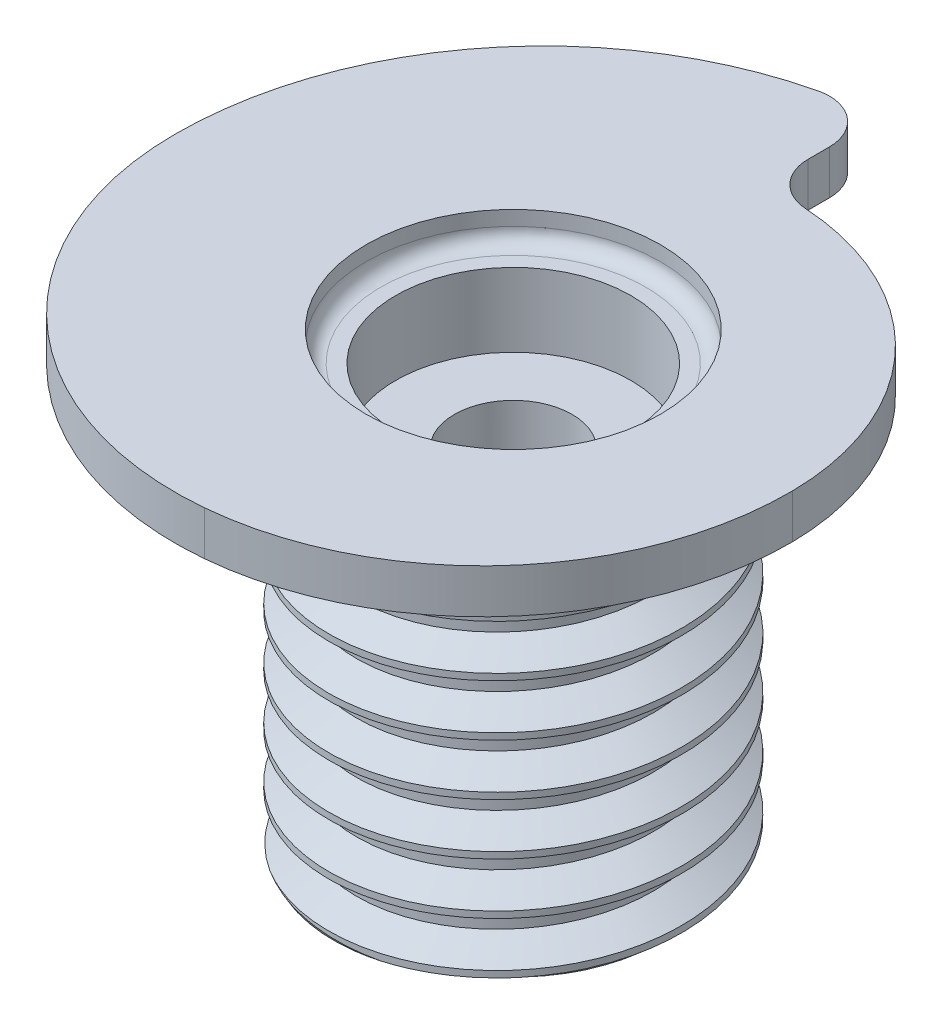
SolidWorks part; units mm, degrees
ref_plane "Front Plane" through (0, 0, 0) normal (0, 0, 1) x (1, 0, 0)
ref_plane "Top Plane" through (0, 0, 0) normal (0, 1, 0) x (1, 0, 0)
ref_plane "Right Plane" through (0, 0, 0) normal (1, 0, 0) x (0, 0, -1)
sketch "Sketch1" plane through (0, 0, 0) normal (1, 0, 0) x (0, 0, -1)
  line L4 (12, 28) -> (12, 0)
  line L6 (0, 0) -> (0, 28) construction
  line L7 (12, 28) -> (4, 28)
  line L10 (4, 28) -> (4, 5)
  line L11 (4, 5) -> (8, 5)
  line L12 (8, 5) -> (8, 0)
  line L13 (8, 0) -> (12, 0)
  dimension "D1" = 8
  dimension "D2" = 8
  dimension "D3" = 5
  dimension "D6" = 28
  dimension "D7" = 12
revolve "Revolve1" add sketch "Sketch1" angle 360 about L6
chamfer "Chamfer1" distance 1 angle 30 1 edges at (0, 0, -12) first distance on face at (0, 28, -12)
thread "Thread1" pitch 3.5 method cut profile "Thread Profile1" start angle 0, offset 0, length 48, pitch 3.5, diameter 24
ref_plane "Plane1" through (-12, 28, 0) normal (0, 0, 1) x (-1, 0, 0)
sketch "Thread Profile1" plane through (-12, 28, 0) normal (0, 0, 1) x (-1, 0, 0)
  line L0 (0, 0) -> (0, 3.5) construction
  line L11 (0, 0) -> (0, 3.0625)
  line L12 (0, 3.0625) -> (-1.8944, 1.9687)
  line L13 (-1.8944, 1.9687) -> (-1.8944, 1.0937)
  line L15 (-1.8944, 1.0937) -> (0, 0)
  line L17 (-1.8944, 1.5312) -> (0, 1.5312) construction
  point P2 (0, 0)
  dimension "Pitch" = 3.5
  dimension "Profile_Angle" = 60
  dimension "Profile_Land" = 0.875
  dimension "Profile_Height" = 1.8944
sketch "Sketch2" plane through (0, 28, 0) normal (0, 1, 0) x (1, 0, 0)
  line L1 (0, 11.547) -> (-10, -5.7735) construction
  line L2 (-10, -5.7735) -> (10, -5.7735) construction
  line L3 (10, -5.7735) -> (0, 11.547) construction
  circle A0 centre (0, 0) radius 5.7735 construction
  circle A1 centre (0, 11.547) radius 1.5
  circle A2 centre (10, -5.7735) radius 1.5
  circle A3 centre (-10, -5.7735) radius 1.5
  dimension "D2" = 3
  dimension "D1" = 20
extrude "Cut-Extrude1" [suppressed] cut sketch "Sketch2" against normal blind 4
sketch "Sketch3" plane through (0, 28, 0) normal (0, 1, 0) x (1, 0, 0)
  line L0 (0, 25) -> (0, -25) construction
  line L1 (-25, 0) -> (25, 0) construction
  line L2 (0, 25) -> (0, 17)
  circle A1 centre (0, 0) radius 17 construction
  circle A2 centre (0, 0) radius 19 construction
  circle A3 centre (0, 0) radius 21 construction
  circle A4 centre (0, 0) radius 23 construction
  circle A5 centre (0, 0) radius 25 construction
  arc A6 (0, 25) -> (-23, 0) centre (2.087, 0) ccw
  arc A7 (-23, 0) -> (0, -21) centre (-1.913, 0) ccw
  arc A8 (0, -21) -> (19, 0) centre (-1.8958, -0.1895) ccw
  arc A9 (19, 0) -> (0, 17) centre (1.7548, -0.1564) ccw
  dimension "D1" = 34
  dimension "D2" = 2
  dimension "D3" = 2
  dimension "D4" = 2
  dimension "D5" = 2
extrude "Boss-Extrude1" add sketch "Sketch3" along normal blind 3
sketch "Sketch6" plane through (0, 31, 0) normal (0, 1, 0) x (1, 0, 0)
  circle A0 centre (0, 0) radius 10
  dimension "D1" = 20
extrude "Cut-Extrude3" cut sketch "Sketch6" against normal blind 2
sketch "Sketch4" plane through (0, 29, 0) normal (0, 1, 0) x (1, 0, 0)
  circle A2 centre (0, 0) radius 8
  dimension "D1" = 16
extrude "Cut-Extrude2" cut sketch "Sketch4" against normal blind 5
fillet "Fillet1" radius 3 2 edges at (0, 29.5, -17) (0, 29.5, -25)
sketch "Sketch5" plane through (0, 31, 0) normal (0, 1, 0) x (1, 0, 0)
  arc A0 (-6.606, 16.744) -> (-18, 0) centre (0, 0) ccw construction
  arc A1 (-7.5235, 19.0695) -> (-20.5, 0) centre (0, 0) ccw
  arc A2 (-5.6885, 14.4184) -> (-15.5, 0) centre (0, 0) ccw
  arc A3 (-5.6885, 14.4184) -> (-7.5235, 19.0695) centre (-6.606, 16.744) ccw
  arc A4 (-20.5, 0) -> (-15.5, 0) centre (-18, 0) ccw
  arc A5 (-8.6169, -12.278) -> (8.6169, -12.278) centre (0, 0) ccw construction
  arc A6 (-9.7658, -13.9151) -> (9.7658, -13.9151) centre (0, 0) ccw
  arc A7 (-7.4679, -10.6409) -> (7.4679, -10.6409) centre (0, 0) ccw
  arc A8 (-7.4679, -10.6409) -> (-9.7658, -13.9151) centre (-8.6169, -12.278) ccw
  arc A9 (9.7658, -13.9151) -> (7.4679, -10.6409) centre (8.6169, -12.278) ccw
  arc A10 (13.9041, 1.6355) -> (6.0016, 12.6484) centre (0, 0) ccw construction
  arc A11 (15.3939, 1.8107) -> (6.6446, 14.0035) centre (0, 0) ccw
  arc A12 (12.4144, 1.4603) -> (5.3586, 11.2932) centre (0, 0) ccw
  arc A13 (12.4144, 1.4603) -> (15.3939, 1.8107) centre (13.9041, 1.6355) ccw
  arc A14 (6.6446, 14.0035) -> (5.3586, 11.2932) centre (6.0016, 12.6484) ccw
  point P4 (-14.8813, 10.1265)
  point P9 (0, -15)
  point P18 (11.3745, 8.1621)
  dimension "D1" = 18
  dimension "D2" = 2.5
  dimension "D3" = 15
  dimension "D4" = 2
  dimension "D5" = 14
  dimension "D6" = 1.5
fillet "Fillet2" radius 1 1 edges at (0, 29, 10)
